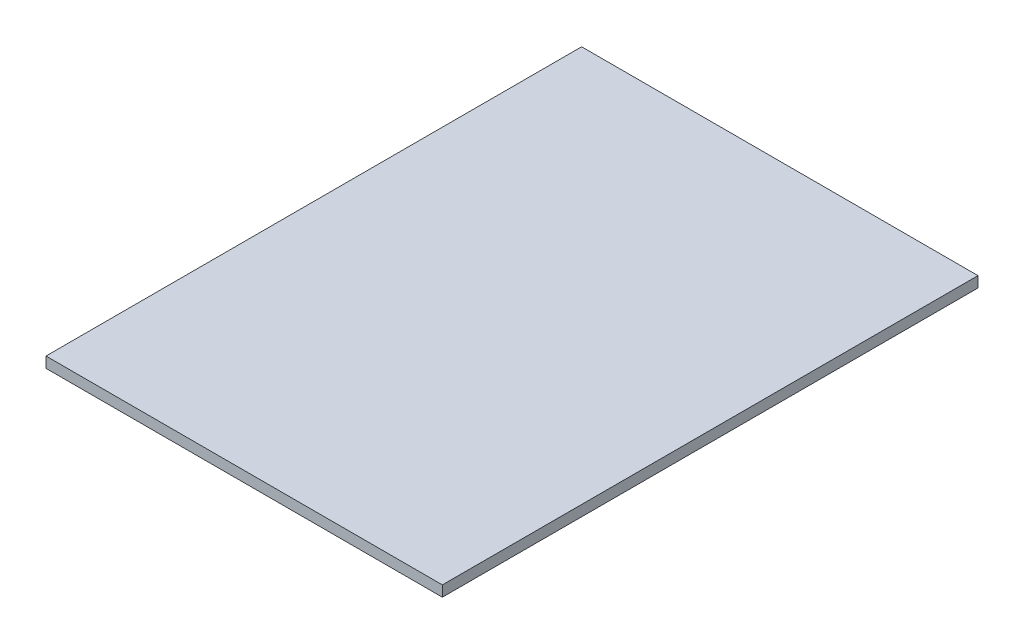
SolidWorks part; units mm, degrees
ref_plane "前视基准面" through (0, 0, 0) normal (0, 0, 1) x (1, 0, 0)
ref_plane "上视基准面" through (0, 0, 0) normal (0, 1, 0) x (1, 0, 0)
ref_plane "右视基准面" through (0, 0, 0) normal (1, 0, 0) x (0, 0, -1)
sketch "草图2" plane through (0, 0, 0) normal (0, 1, 0) x (1, 0, 0)
  line L1 (-37, -50) -> (37, -50)
  line L2 (-37, -50) -> (-37, 50)
  line L3 (-37, 50) -> (37, 50)
  line L4 (37, -50) -> (37, 50)
  line L5 (-37, -50) -> (37, 50) construction
  line L6 (-37, 50) -> (37, -50) construction
  point P0 (0, 0)
  dimension "D1" = 74
  dimension "D2" = 100
extrude "凸台-拉伸1" add sketch "草图2" along normal blind 2
